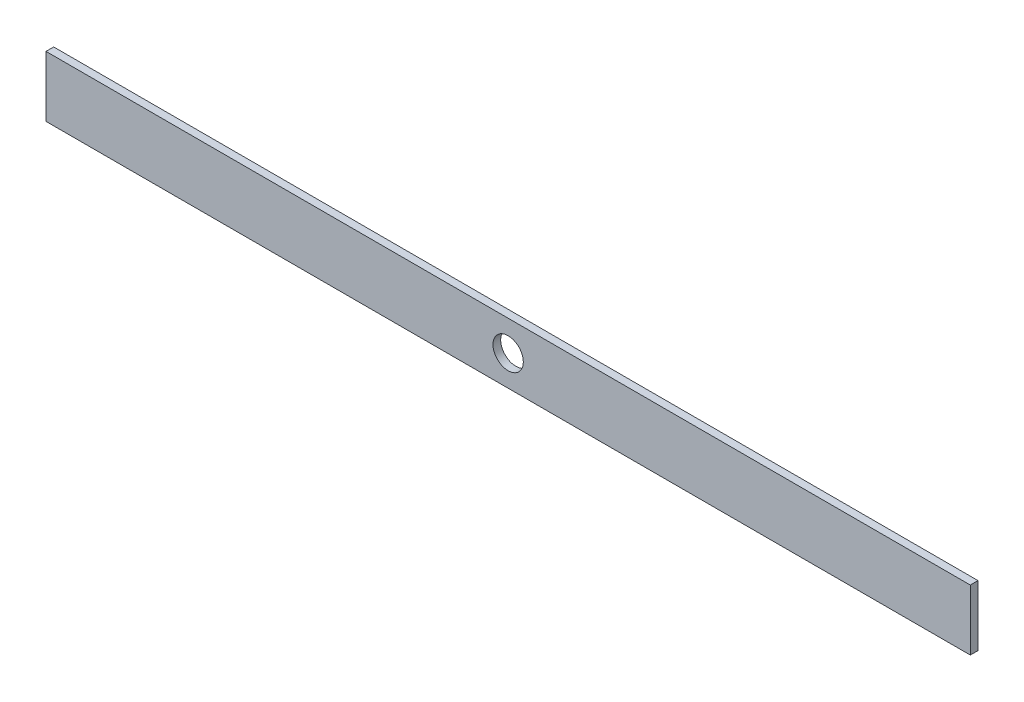
SolidWorks part; units mm, degrees
material "ABS"
ref_plane "Front Plane" through (0, 0, 0) normal (0, 0, 1) x (1, 0, 0)
ref_plane "Top Plane" through (0, 0, 0) normal (0, 1, 0) x (1, 0, 0)
ref_plane "Right Plane" through (0, 0, 0) normal (1, 0, 0) x (0, 0, -1)
sketch "Sketch1" plane through (0, 0, 0) normal (0, 0, 1) x (1, 0, 0)
  line L0 (55, 0) -> (-55, 0) construction
  line L1 (-381, -25) -> (381, -25)
  line L2 (-381, -25) -> (-381, 25)
  line L3 (-381, 25) -> (381, 25)
  line L4 (381, -25) -> (381, 25)
  line L5 (-381, -25) -> (381, 25) construction
  line L6 (-381, 25) -> (381, -25) construction
  point P0 (0, 0)
  dimension "D1" = 762
  dimension "D2" = 50
extrude "Boss-Extrude1" add sketch "Sketch1" along normal blind 6.35
sketch "Sketch2" plane through (0, 0, 6.35) normal (0, 0, 1) x (1, 0, 0)
  line L4 (381, -25) -> (381, 25)
  line L5 (381, 25) -> (-381, 25)
  line L6 (-381, 25) -> (-381, -25)
  line L7 (-381, -25) -> (381, -25)
  line L8 (381, -25) -> (381, 25) construction
  line L9 (381, 25) -> (-381, 25) construction
  line L10 (-381, 25) -> (-381, -25) construction
  line L11 (-381, -25) -> (381, -25) construction
  circle A0 centre (0, 0) radius 12.5
  dimension "D2" = 25
  dimension "D1" = 0
extrude "Cut-Extrude1" cut sketch "Sketch2" against normal through all
